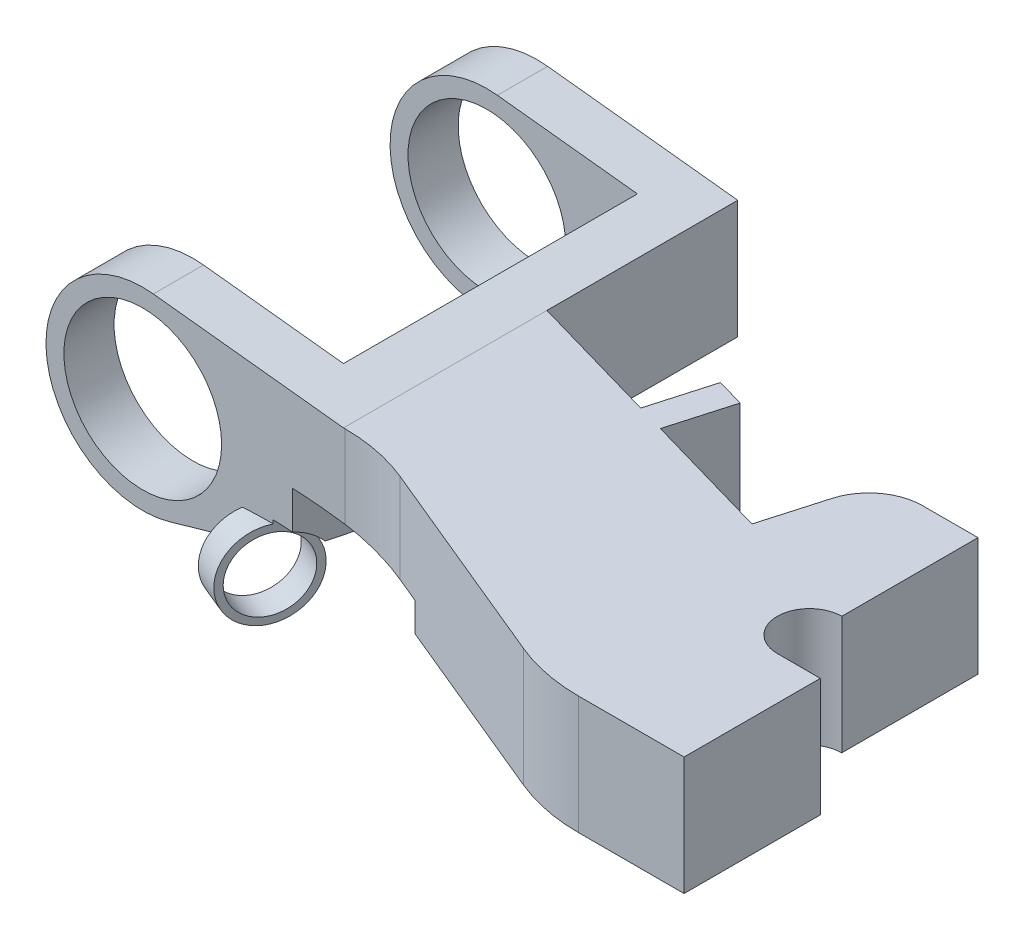
SolidWorks part; units mm, degrees
ref_plane "Спереди" through (0, 0, 0) normal (0, 0, 1) x (1, 0, 0)
ref_plane "Сверху" through (0, 0, 0) normal (0, 1, 0) x (1, 0, 0)
ref_plane "Справа" through (0, 0, 0) normal (1, 0, 0) x (0, 0, -1)
sketch "Эскиз8" plane through (0, 0, 0) normal (0, 1, 0) x (1, 0, 0)
  line L0 (-31.6673, 77.5) -> (-62.0836, 77.5) construction
  line L1 (-85, 43.6529) -> (-6, 21) construction
  line L2 (-106, 13.5) -> (-92.5, 13.5)
  line L3 (-92.5, 13.5) -> (-92.5, 6.5)
  line L4 (-92.5, 6.5) -> (-119.5, 6.5)
  line L6 (-119.5, 6.5) -> (-119.5, 13.5)
  line L7 (-119.5, 13.5) -> (-106, 13.5)
  line L8 (-117, 28.0456) -> (-95, 28.0456) construction
  line L31 (-92.5, 61.5) -> (-119.5, 61.5)
  line L32 (-119.5, 61.5) -> (-119.5, 54.5)
  line L33 (-119.5, 54.5) -> (-92.5, 54.5)
  line L34 (-92.5, 54.5) -> (-92.5, 61.5)
  line L37 (-62.0836, 77.5) -> (-62.0836, 61.5) construction
  line L38 (-62.0836, 61.5) -> (-92.5, 61.5) construction
  line L39 (-11.6673, -9.5) -> (-52.0836, -9.5) construction
  line L44 (-52.0836, -9.5) -> (-52.0836, 6.5) construction
  line L45 (-42.6378, 23.1833) -> (-38.3121, 21.943)
  line L46 (-17.6673, 16.0231) -> (-17.6673, 18.5) construction
  line L47 (-52.0836, 6.5) -> (-92.5, 6.5) construction
  line L48 (-106, 28.0456) -> (-85, 28.0456) construction
  line L52 (-92.5, 54.5) -> (-85, 54.5)
  line L53 (-85, 54.5) -> (-85, 13.5)
  line L54 (-85, 13.5) -> (-92.5, 13.5)
  line L56 (-6, 21) -> (-6, 28) construction
  line L59 (-78, 61.5) -> (-78, 63.0226)
  line L60 (-35.418, 32.0362) -> (-39.7436, 33.2766)
  line L61 (-78, 61.5) -> (-78, 33.3233)
  line L64 (-11.6673, 9.5) -> (-17.6673, 9.5)
  line L65 (-17.6673, 37.5) -> (-17.6673, 18.5) construction
  line L67 (-38.3121, 21.943) -> (-35.418, 32.0362)
  line L68 (-41.1218, 28.4703) -> (-42.6378, 23.1833) construction
  line L69 (-60.3189, 28.2533) -> (-57.4247, 38.3465) construction
  line L70 (-39.7436, 33.2766) -> (-41.1218, 28.4703)
  line L71 (-41.1218, 28.4703) -> (-36.7961, 27.2299)
  line L72 (-42.6378, 23.1833) -> (-78, 33.3233)
  line L79 (-38.3121, 21.943) -> (-17.6673, 16.0231) construction
  line L82 (-35.418, 32.0362) -> (-33.8512, 37.5) construction
  line L83 (-57.665, 38.4155) -> (-61.5101, 39.518)
  line L84 (-57.4247, 38.3465) -> (-57.665, 38.4155)
  line L85 (-57.4247, 38.3465) -> (-57.1844, 38.2776)
  line L86 (-57.1844, 38.2776) -> (-60.0786, 28.1844)
  line L87 (-61.5101, 39.518) -> (-62.8883, 34.7117)
  line L88 (-62.8883, 34.7117) -> (-58.5626, 33.4713)
  line L89 (-57.1844, 38.2776) -> (-53.3394, 37.1751)
  line L90 (-53.3394, 37.1751) -> (-56.2335, 27.0818)
  line L91 (-62.8883, 34.7117) -> (-64.4043, 29.4248) construction
  line L92 (-33.8512, 37.5) -> (-17.6673, 37.5) construction
  circle A1 centre (-106, 28.0456) radius 11
  circle A6 centre (-106, 28.0456) radius 13.5
  arc A8 (-17.6673, 18.5) -> (-17.6673, 9.5) centre (-17.6673, 14) ccw
  spline S0 degree 3 poles (-31.6673, 77.5) (-62.0836, 77.5) (-62.0836, 61.5) (-92.5, 61.5) knots 0 0 0 0 1 1 1 1
  spline S1 degree 3 poles (-11.6673, -9.5) (-52.0836, -9.5) (-52.0836, 6.5) (-92.5, 6.5) knots 0 0 0 0 1 1 1 1
  spline S3 degree 2 poles (-35.418, 32.0362) (-33.8512, 37.5) (-17.6673, 37.5) knots 0 0 0 1 1 1
  point P48 (-60.3189, 28.2533)
sketch "Эскиз10" plane through (0, 0, 0) normal (0, 1, 0) x (1, 0, 0)
  line L0 (-34.4146, 72.312) -> (-60.5171, 61.5) construction
  line L2 (-92.5, 61.5) -> (-78, 61.5)
  line L4 (-78, 34.8837) -> (-78, 61.5)
  line L5 (-20.4853, 37.5) -> (-20.4853, 18.5)
  line L9 (-14.4853, 9.5) -> (-14.4853, -9.5)
  line L11 (-34.1789, -9.5) -> (-14.4853, -9.5)
  line L13 (-92.5, 54.5) -> (-85, 54.5)
  line L14 (-85, 54.5) -> (-85, 13.5)
  line L15 (-85, 13.5) -> (-92.5, 13.5)
  line L21 (-92.5, 6.5) -> (-72.8063, 6.5)
  line L22 (-14.4853, 9.5) -> (-20.4853, 9.5)
  line L23 (-20.4853, 9.5) -> (-20.4853, 18.5) construction
  line L24 (-35.418, 32.0362) -> (-37.8987, 23.3849)
  line L27 (-59.6651, 29.6263) -> (-57.1844, 38.2776)
  line L28 (-57.1844, 38.2776) -> (-53.3394, 37.1751)
  line L29 (-53.3394, 37.1751) -> (-55.8201, 28.5237)
  line L31 (-53.4926, -9.5) -> (-53.4926, 6.5) construction
  line L32 (-92.5, 61.5) -> (-119.5, 61.5)
  line L34 (-92.5, 54.5) -> (-119.5, 54.5)
  line L35 (-119.5, 61.5) -> (-119.5, 54.5)
  line L36 (-92.5, 13.5) -> (-119.5, 13.5)
  line L38 (-92.5, 6.5) -> (-119.5, 6.5)
  line L39 (-119.5, 13.5) -> (-119.5, 6.5)
  line L40 (-78, 34.8837) -> (-59.6651, 29.6263)
  line L41 (-53.4926, -1.5) -> (-72.8063, 6.5)
  line L42 (-53.4926, -1.5) -> (-34.1789, -9.5)
  line L43 (-55.8201, 28.5237) -> (-37.8987, 23.3849)
  line L44 (-20.4853, 37.5) -> (-28.1673, 37.5)
  line L45 (-35.418, 32.0362) -> (-28.1673, 29.9571) construction
  line L46 (-28.1673, 37.5) -> (-28.1673, 29.9571) construction
  arc A0 (-20.4853, 18.5) -> (-20.4853, 9.5) centre (-20.4853, 14) ccw
  arc A2 (-35.418, 32.0362) -> (-28.1673, 37.5) centre (-28.1673, 29.9571) cw
  point P15 (0, 0)
  point P16 (0, 0)
  point P27 (0, 0)
  point P28 (0, 0)
extrude "Бобышка-Вытянуть1" add sketch "Эскиз10" along normal mid plane 27 separate body contours L24 L29 L28 L27 L4 L32 L35 L34 L13 L14 L15 L36 L39 L38 region at (-59.1919, 0, -19.6134)
sketch "Эскиз11" plane through (0, 0, 0) normal (0, 0, 1) x (1, 0, 0)
  line L10 (-11.6673, -6) -> (-11.6673, 10.5)
  line L16 (-106, 0) -> (-11.6673, 0) construction
  line L31 (-11.6673, 10.5) -> (-78, 10.5)
  line L50 (-119.5, 13.5) -> (-11.6673, 13.5)
  line L51 (-119.5, 13.5) -> (-119.5, -13.5)
  line L52 (-119.5, -13.5) -> (-11.6673, -13.5)
  line L53 (-11.6673, 13.5) -> (-11.6673, -13.5)
  line L55 (-78, 10.5) -> (-78, -6)
  line L56 (-78, -6) -> (-11.6673, -6)
  line L57 (-78, -6) -> (-102.2714, -12.9749)
  line L58 (-78, 10.5) -> (-104.5232, 13.419)
  circle A2 centre (-106, 0) radius 11
  circle A5 centre (-106, 0) radius 13.5
extrude "Вырез-Вытянуть1" cut sketch "Эскиз11" against normal through all both and the other way through all contours A2 | A5 L51 L52 | A5 L50 L51 | L52 L53 | L50 L53 region at (-51.7306, -9.9565, 0) region at (-52.0379, 12.0853, 0) region at (-116.4845, -10.4845, 0) region at (-116.4845, 10.4845, 0) region at (-106, 0, 0)
sketch "Эскиз12" plane through (-62.9818, 0, -18.0597) normal (-0.9613, 0, -0.2756) x (-0.2756, 0, 0.9613)
  line L0 (-18.5327, 0) -> (-18.5327, -6) construction
  line L1 (-21.0327, 0) -> (-18.5327, 0) construction
  line L2 (-21.0327, -6) -> (-12.0327, -6) construction
  circle A0 centre (-18.5327, 0) radius 2.5
extrude "Бобышка-Вытянуть2" add sketch "Эскиз12" along normal blind 4.5
sketch "Эскиз13" plane through (-41.2153, 0, -11.8183) normal (-0.9613, 0, -0.2756) x (-0.2756, 0, 0.9613)
  line L0 (-21.0327, 0) -> (-18.5327, 0) construction
  line L2 (-18.5327, 0) -> (-18.5327, -6) construction
  line L3 (-12.0327, -6) -> (-21.0327, -6) construction
  circle A0 centre (-18.5327, 0) radius 2.5
extrude "Бобышка-Вытянуть3" add sketch "Эскиз13" along normal blind 4.5
fillet "Скругление1" radius 25 2 edges at (-34.1789, 2.25, 9.5) (-72.8063, 2.25, -6.5)
sketch "Эскиз15" plane through (-80.9415, 0, -33.5271) normal (-0.9239, 0, -0.3827) x (-0.3827, 0, 0.9239)
  circle A0 centre (27.9359, -12) radius 5
  circle A1 centre (27.9359, -12) radius 6
extrude "Бобышка-Вытянуть4" add sketch "Эскиз15" against normal blind 4
sketch3d "Трехмерный эскиз2"
  line L0 (-75.2961, -2.5, 5.5433) -> (-82.6968, -2.5, 2.4778)
  line L1 (-82.6968, -2.5, 2.4778) -> (-78.1046, -21.5, -8.6087)
ref_plane "Плоскость3" through (-9.7155, -16.0344, 23.4553) normal (-0.3236, -0.534, 0.7811) x (0.9462, -0.1826, 0.2671)
sketch "Эскиз18" plane through (-9.7155, -16.0344, 23.4553) normal (-0.3236, -0.534, 0.7811) x (0.9462, -0.1826, 0.2671)
  line L0 (-82.0108, -7.1077) -> (-81.0339, -6.8941)
  line L3 (-81.0339, -6.8941) -> (-81.2236, -6.0364)
  line L4 (-83.4754, -7.4316) -> (-83.9636, -7.5396)
  line L5 (-80.5962, -3.4484) -> (-79.6779, -2.2435)
  line L6 (-83.9636, -7.5396) -> (-87.8692, -8.4035) construction
  line L7 (-77.1301, -0.6655) -> (-69.3087, 1.0645)
  line L9 (-62.7353, -0.8951) -> (-62.0049, -4.1972)
  line L18 (-69.4167, 1.5527) -> (-63.0749, 2.9554)
  line L20 (-62.2471, -0.7871) -> (-63.0749, 2.9554)
  line L22 (-69.3087, 1.0645) -> (-69.4167, 1.5527) construction
  line L24 (-62.7353, -0.8951) -> (-62.2471, -0.7871) construction
  line L32 (-62.2471, -0.7871) -> (-61.5167, -4.0892)
  line L39 (-83.4754, -7.4316) -> (-82.0108, -7.1077)
  line L41 (-77.1301, -0.6655) -> (-77.2381, -0.1773) construction
  line L42 (-77.2381, -0.1773) -> (-69.4167, 1.5527)
  line L43 (-73.2194, 0.1995) -> (-73.3274, 0.6877) construction
  line L45 (-77.2381, -0.1773) -> (-82.7615, -1.399)
  line L46 (-81.2236, -6.0364) -> (-81.7118, -6.1443) construction
  line L47 (-83.9636, -7.5396) -> (-84.0716, -7.0514)
  line L48 (-84.0716, -7.0514) -> (-81.6306, -6.5115)
  line L49 (-81.6306, -6.5115) -> (-82.7615, -1.399)
  line L50 (-80.5962, -3.4484) -> (-80.9938, -3.1453) construction
  line L51 (-79.6779, -2.2435) -> (-80.0755, -1.9404) construction
  line L52 (-80.137, -2.8459) -> (-80.5347, -2.5428) construction
  line L53 (-80.9938, -3.1453) -> (-80.0755, -1.9404) construction
  line L54 (-69.3087, 1.0645) -> (-68.5889, -2.1898) construction
  line L55 (-62.7353, -0.8951) -> (-68.5889, -2.1898) construction
  line L56 (-83.9636, -7.5396) -> (-82.6678, -13.398)
  line L57 (-82.6678, -13.398) -> (-60.5403, -8.5037)
  line L58 (-61.5167, -4.0892) -> (-60.5403, -8.5037)
  spline S1 degree 3 poles (-81.2236, -6.0364) (-81.4199, -5.1489) (-81.1996, -4.2401) (-80.5962, -3.4484) knots 0 0 0 0 1 1 1 1 weights 1 0.949253 0.949253 1
  spline S3 degree 3 poles (-79.6779, -2.2435) (-79.0744, -1.4518) (-78.1798, -0.8977) (-77.1301, -0.6655) knots 0 0 0 0 1 1 1 1 weights 1 0.949253 0.949253 1
  spline S5 degree 3 poles (-69.3087, 1.0645) (-65.7664, 1.848) (-63.0107, 1.0266) (-62.7353, -0.8951) knots 0 0 0 0 1 1 1 1 weights 1 0.79515 0.79515 1
revolve "Вырез-Повернуть2" cut sketch "Эскиз18" angle 360 about L57 region at (-78.1506, -7.1809, 1.161)
sketch "Эскиз19" plane through (-77.246, 0, -31.9963) normal (0.9239, 0, 0.3827) x (0.3827, 0, -0.9239)
  line L0 (-33.9359, -2.5) -> (-21.9359, -21.5) construction
  circle A0 centre (-27.9359, -12) radius 5
extrude "Вырез-Вытянуть3" cut sketch "Эскиз19" against normal blind 4
sketch "Эскиз20" plane through (-80.9415, 0, -33.5271) normal (0.9239, 0, 0.3827) x (0.3827, 0, -0.9239)
  line L0 (-33.9359, -2.5) -> (-21.9359, -21.5) construction
  circle A0 centre (-27.9359, -12) radius 5
extrude "Вырез-Вытянуть4" cut sketch "Эскиз20" against normal blind 0.5
